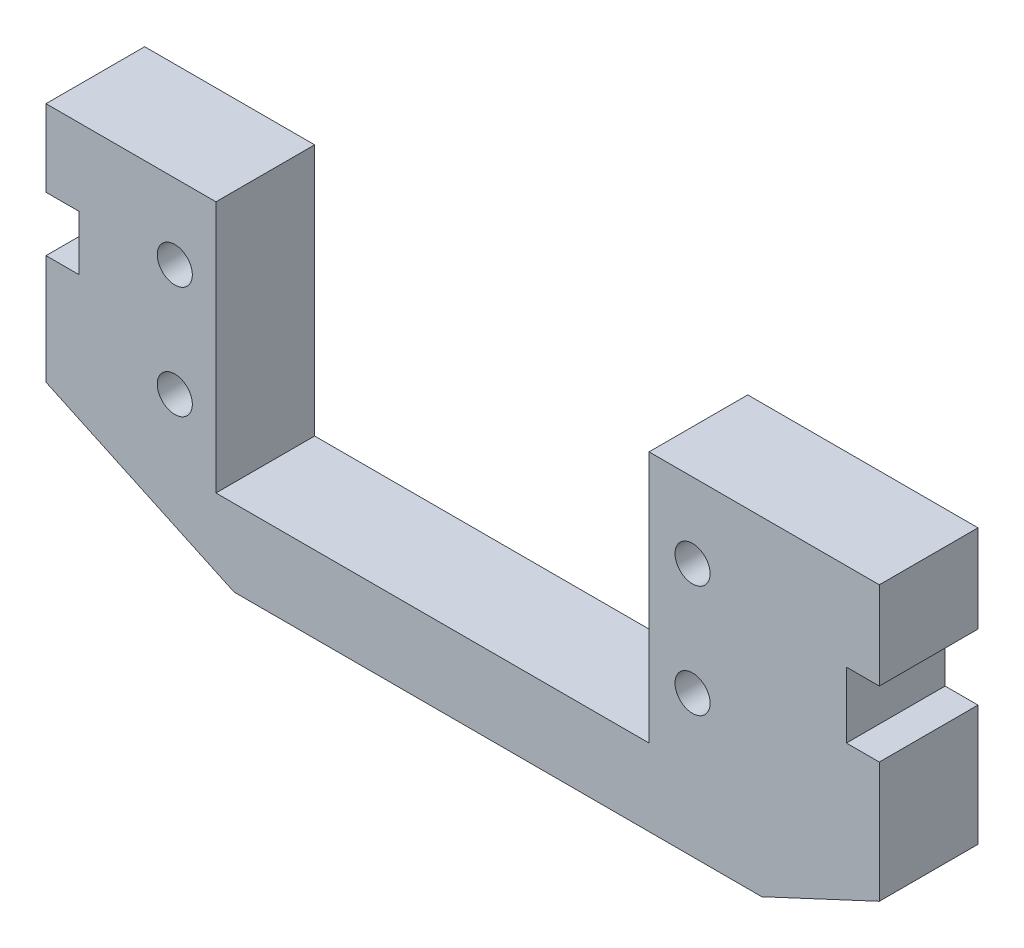
SolidWorks part; units mm, degrees
material "Plywood"
ref_plane "Plan de face" through (0, 0, 0) normal (0, 0, 1) x (1, 0, 0)
ref_plane "Plan de dessus" through (0, 0, 0) normal (0, 1, 0) x (1, 0, 0)
ref_plane "Plan de droite" through (0, 0, 0) normal (1, 0, 0) x (0, 0, -1)
sketch "Esquisse1" plane through (0, 0, 0) normal (0, 0, 1) x (1, 0, 0)
  line L0 (0, 0) -> (0, -30)
  line L1 (0, -30) -> (76, -30)
  line L2 (76, -30) -> (76, 0)
  line L3 (76, 0) -> (55, 0)
  line L4 (55, 0) -> (55, -23)
  line L5 (55, -23) -> (15.5, -23)
  line L6 (15.5, -23) -> (15.5, 0)
  line L7 (15.5, 0) -> (0, 0)
  dimension "D1" = 39.5
  dimension "D2" = 15.5
  dimension "D3" = 30
  dimension "D4" = 76
  dimension "D5" = 23
extrude "Boss.-Extru.1" add sketch "Esquisse1" along normal blind 9
sketch "Esquisse2" plane through (0, 0, 0) normal (0, 0, -1) x (-1, 0, 0)
  circle A0 centre (-11.7466, -17.0763) radius 1.6
  circle A1 centre (-11.7466, -6.8488) radius 1.6
  circle A2 centre (-58.9661, -17.0763) radius 1.6
  circle A3 centre (-58.9661, -6.8488) radius 1.6
  dimension "D1" = 3.2
  dimension "D2" = 3.2
  dimension "D3" = 3.2
  dimension "D4" = 3.2
extrude "Enlèv. mat.-Extru.1" cut sketch "Esquisse2" against normal through all
chamfer "Chanfrein1" distance 8 angle 65 1 edges at (0, -30, 4.5) first distance on face at (0, -15, 4.5)
chamfer "Chanfrein2" distance 5 angle 65 1 edges at (76, -30, 4.5) first distance on face at (76, -15, 4.5)
sketch "Esquisse3" plane through (0, 0, 9) normal (0, 0, 1) x (1, 0, 0)
  line L0 (76, -25) -> (76, 0) construction
  line L1 (76, -8) -> (73, -8)
  line L2 (76, -8) -> (76, -14)
  line L3 (76, -14) -> (73, -14)
  line L4 (73, -8) -> (73, -14)
  line L5 (76, 0) -> (55, 0) construction
  line L6 (0, 0) -> (0, -22) construction
  line L7 (0, -7) -> (3, -7)
  line L8 (0, -7) -> (0, -12)
  line L9 (0, -12) -> (3, -12)
  line L10 (3, -7) -> (3, -12)
  line L11 (15.5, 0) -> (0, 0) construction
  dimension "D1" = 8
  dimension "D2" = 6
  dimension "D3" = 3
  dimension "D4" = 3
  dimension "D5" = 7
  dimension "D6" = 5
extrude "Enlèv. mat.-Extru.2" cut sketch "Esquisse3" against normal through all
